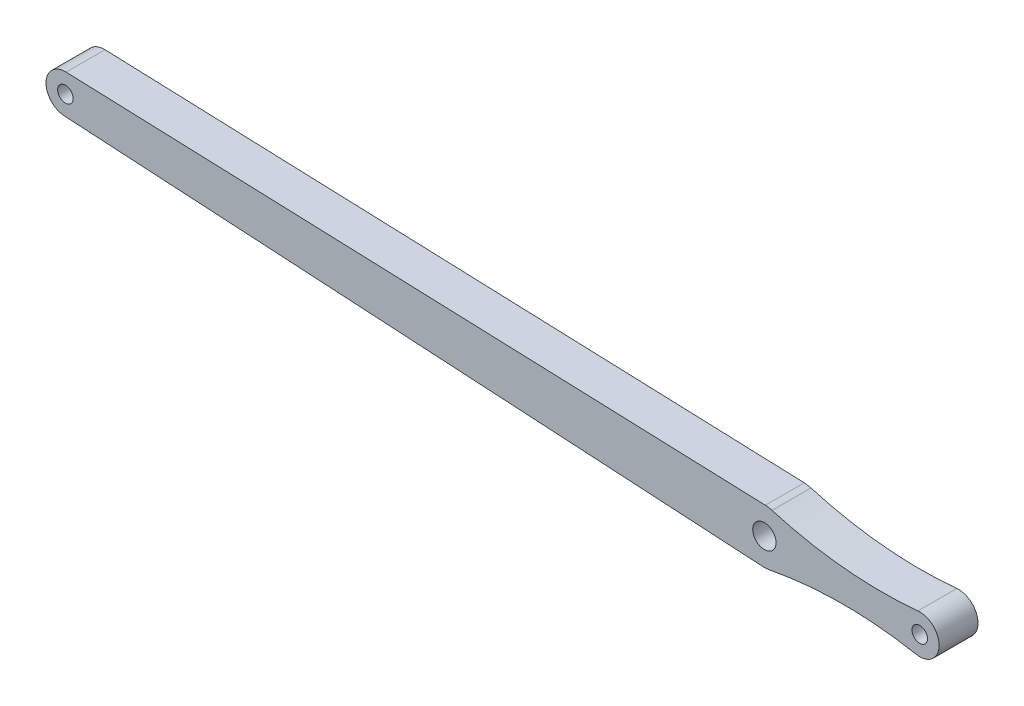
SolidWorks part; units mm, degrees
ref_plane "Front Plane" through (0, 0, 0) normal (0, 0, 1) x (1, 0, 0)
ref_plane "Top Plane" through (0, 0, 0) normal (0, 1, 0) x (1, 0, 0)
ref_plane "Right Plane" through (0, 0, 0) normal (1, 0, 0) x (0, 0, -1)
sketch "Sketch1" plane through (0, 0, 0) normal (0, 0, 1) x (1, 0, 0)
  line L0 (-2.0729, 133.5025) -> (-181.9424, 140.0573)
  line L3 (-2.7381, 119.5192) -> (-182.4176, 130.0692)
  circle A2 centre (-2.3278, 126.5072) radius 7
  circle A3 centre (-182.1245, 135.0606) radius 5
  circle A4 centre (37.627, 124.6064) radius 5
  arc A5 (-0.3514, 133.2223) -> (37.163, 129.5848) centre (27.884, 229.1534) ccw
  arc A6 (36.6925, 119.6945) -> (-0.9978, 119.6347) centre (18.0032, 21.4565) ccw
  circle A7 centre (-182.1245, 135.0606) radius 2 construction
  circle A8 centre (-182.1245, 135.0606) radius 2
  circle A9 centre (-2.3278, 126.5072) radius 3 construction
  circle A10 centre (-2.3278, 126.5072) radius 3
  circle A11 centre (37.627, 124.6064) radius 2 construction
  circle A12 centre (37.627, 124.6064) radius 2
  dimension "D1" = 14
  dimension "D2" = 10
  dimension "D3" = 10
  dimension "D4" = 100
  dimension "D5" = 100
extrude "Boss-Extrude1" add sketch "Sketch1" along normal blind 5 and the other way blind 5 contours A3 L3 A2 L0 | A3 | A2 | A6 A4 A5 A2 | A4 region at (-88.5349, 130.6083, 0) region at (-1.2352, 133.2208, 0) region at (-178.627, 138.433, 0) region at (17.7992, 125.5497, 0) region at (40.8992, 128.1978, 0)
